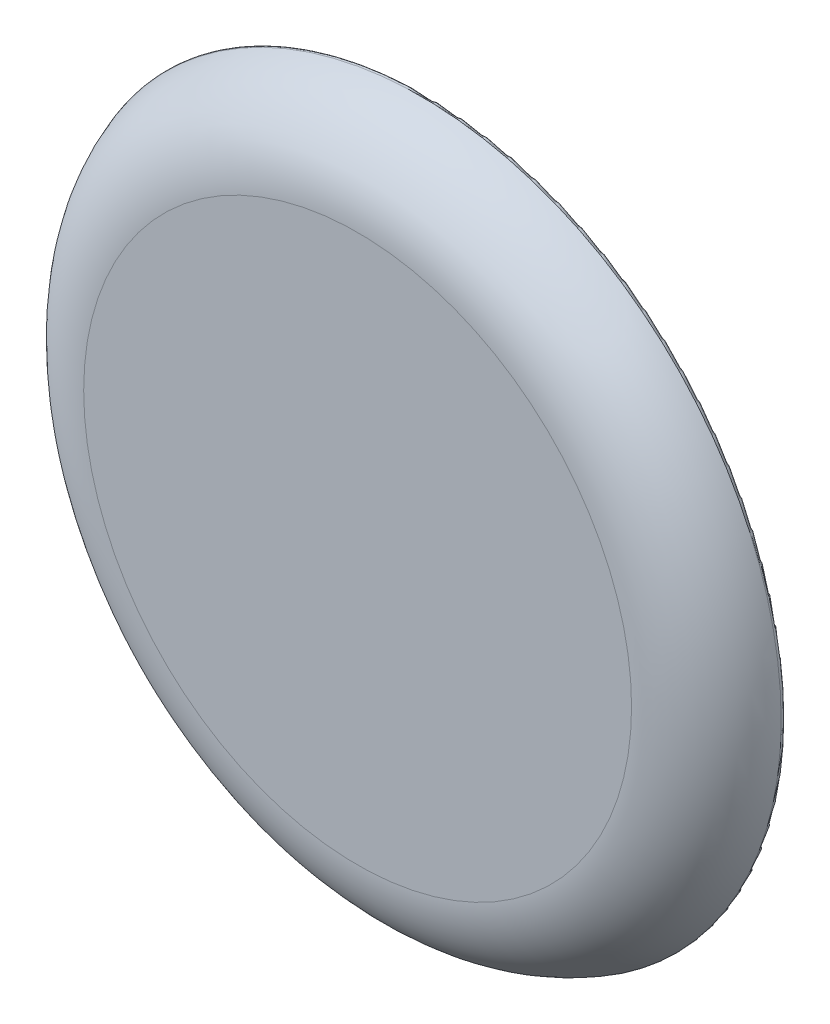
SolidWorks part; units mm, degrees
material "ABS"
ref_plane "Front Plane" through (0, 0, 0) normal (0, 0, 1) x (1, 0, 0)
ref_plane "Top Plane" through (0, 0, 0) normal (0, 1, 0) x (1, 0, 0)
ref_plane "Right Plane" through (0, 0, 0) normal (1, 0, 0) x (0, 0, -1)
sketch "Sketch1" plane through (0, 0, 0) normal (0, 0, 1) x (1, 0, 0)
  circle A0 centre (-86.2647, 57.4705) radius 16
  dimension "D1" = 32
extrude "Boss-Extrude1" add sketch "Sketch1" along normal blind 3
fillet "Fillet1" radius 4 1 edges at (-70.2647, 57.4705, 3)
fillet "Fillet2" radius 0.15 1 edges at (-70.2647, 57.4705, 0)
sketch "Sketch2" plane through (0, 0, 0) normal (0, 0, -1) x (-1, 0, 0)
  circle A0 centre (86.2647, 57.4705) radius 11.05
  circle A1 centre (86.2647, 57.4705) radius 15.9444 construction
  circle A2 centre (86.2647, 57.4705) radius 7.75
  dimension "D1" = 22.1
  dimension "D2" = 15.5
extrude "Boss-Extrude2" add sketch "Sketch2" along normal blind 2
fillet "Fillet3" radius 0.25 1 edges at (-97.3147, 57.4705, -2)
sketch "Sketch3" plane through (0, 0, 3) normal (0, 0, 1) x (1, 0, 0)
  line L0 (200, -304.7195) -> (1000, -304.7195) construction
  line L1 (-96.0533, 60.3442) -> (-88.8282, 60.3442)
  line L2 (-88.8282, 60.3442) -> (-89.4414, 55.8919)
  line L3 (-91.5868, 54.0864) -> (-98.1673, 54.0864)
  line L4 (-98.7549, 54.7967) -> (-98.0053, 58.7292)
  line L7 (-93.0529, 58.8626) -> (-92.1558, 58.8626)
  line L8 (-92.1558, 58.8626) -> (-92.1558, 59.3709)
  line L9 (-92.1558, 59.3709) -> (-94.0651, 59.3709)
  line L11 (-94.6653, 55.5797) -> (-95.5624, 55.5797)
  line L12 (-95.5624, 55.5797) -> (-95.5624, 55.0714)
  line L13 (-95.5624, 55.0714) -> (-93.653, 55.0714)
  line L15 (-94.0651, 59.3709) -> (-94.6653, 55.5797)
  line L16 (-93.653, 55.0714) -> (-93.0529, 58.8626)
  line L25 (-83.3157, 58.8626) -> (-82.4186, 58.8626)
  line L26 (-82.4186, 58.8626) -> (-82.4186, 59.3709)
  line L27 (-82.4186, 59.3709) -> (-84.3279, 59.3709)
  line L28 (-84.9281, 55.5797) -> (-85.8252, 55.5797)
  line L29 (-85.8252, 55.5797) -> (-85.8252, 55.0714)
  line L30 (-85.8252, 55.0714) -> (-83.9158, 55.0714)
  line L31 (-84.3279, 59.3709) -> (-84.9281, 55.5797)
  line L32 (-83.9158, 55.0714) -> (-83.3157, 58.8626)
  line L33 (-83.3559, 61.7388) -> (-83.3559, 61.1023)
  line L34 (-83.3559, 61.1023) -> (-82.6042, 60.954)
  line L35 (-82.6042, 60.954) -> (-82.6042, 60.3442)
  line L36 (-82.6042, 60.3442) -> (-86.8609, 60.3442)
  line L37 (-88.3308, 59.0629) -> (-88.9343, 54.6817)
  line L38 (-88.4154, 54.0864) -> (-81.4817, 54.0864)
  line L39 (-79.5512, 55.7692) -> (-78.7289, 61.7388)
  line L40 (-78.7289, 61.7388) -> (-83.3559, 61.7388)
  line L41 (-78.7157, 60.3442) -> (-74.1415, 60.3442)
  line L42 (-78.2626, 61.8189) -> (-74.1847, 61.8189)
  line L43 (-78.2626, 61.8189) -> (-78.2626, 60.7665)
  line L44 (-78.2626, 60.7665) -> (-74.1847, 60.7665)
  line L45 (-74.1847, 61.8189) -> (-74.1847, 60.7665)
  line L46 (-74.1415, 60.3442) -> (-74.7547, 55.8919)
  line L47 (-78.7157, 60.3442) -> (-78.7157, 59.3709)
  line L48 (-78.7157, 59.3709) -> (-78.004, 59.3709)
  line L49 (-78.004, 59.3709) -> (-78.004, 58.7006)
  line L50 (-78.004, 58.7006) -> (-78.5981, 58.7006)
  line L51 (-78.5981, 58.7006) -> (-79.2272, 54.133)
  line L52 (-79.2272, 54.133) -> (-76.7726, 54.133)
  arc A0 (-98.0053, 58.7292) -> (-96.0533, 60.3442) centre (-96.0533, 58.3571) cw
  arc A1 (-98.7549, 54.7967) -> (-98.1673, 54.0864) centre (-98.1673, 54.6846) ccw
  arc A2 (-91.5868, 54.0864) -> (-89.4414, 55.8919) centre (-91.5142, 56.1774) ccw
  arc A3 (-88.3308, 59.0629) -> (-86.8609, 60.3442) centre (-86.8609, 58.8604) cw
  arc A4 (-88.9343, 54.6817) -> (-88.4154, 54.0864) centre (-88.4154, 54.6102) ccw
  arc A5 (-81.4817, 54.0864) -> (-79.5512, 55.7692) centre (-81.4817, 56.0351) ccw
  arc A6 (-76.7726, 54.133) -> (-74.7547, 55.8919) centre (-76.7726, 56.1698) ccw
extrude "Cut-Extrude1" [suppressed] cut sketch "Sketch3" against normal blind 0.5
fillet "Fillet4" [suppressed] radius 0.05
